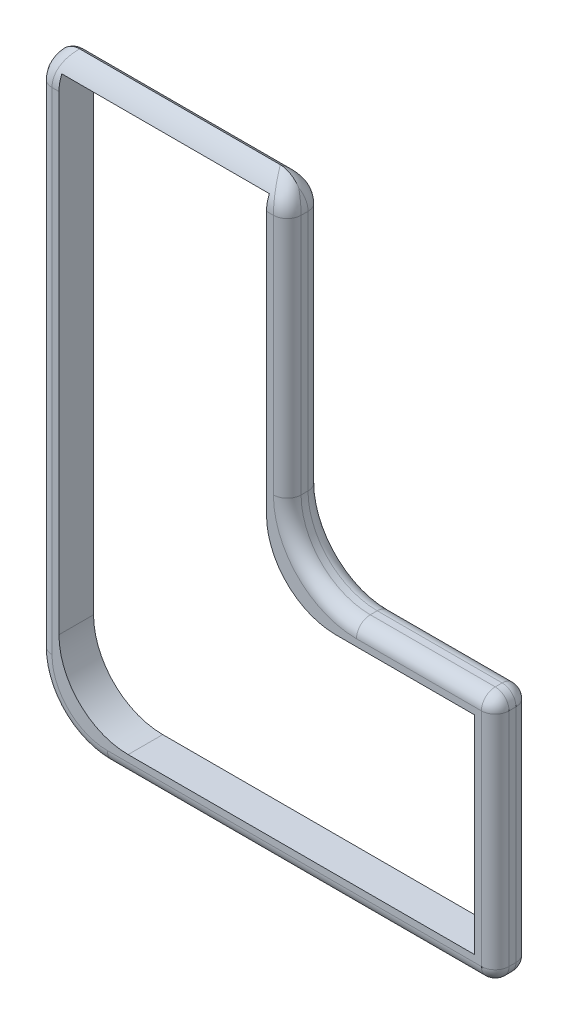
SolidWorks part; units mm, degrees
ref_plane "Front Plane" through (0, 0, 0) normal (0, 0, 1) x (1, 0, 0)
ref_plane "Top Plane" through (0, 0, 0) normal (0, 1, 0) x (1, 0, 0)
ref_plane "Right Plane" through (0, 0, 0) normal (1, 0, 0) x (0, 0, -1)
sketch "Sketch3" plane through (0, 0, 0) normal (0, 0, 1) x (1, 0, 0)
  line L0 (0.15, 0.4) -> (0.15, 0)
  line L1 (-0.15, 0.4) -> (0.15, 0.4)
  line L2 (-0.15, 0.4) -> (-0.15, -0.3)
  line L3 (-0.05, -0.4) -> (0.15, -0.4)
  line L4 (-0.15, 0.43) -> (0.18, 0.43)
  line L5 (-0.15, 0.4) -> (0.15, -0.4) construction
  line L6 (-0.15, -0.4) -> (0.15, 0.4) construction
  line L7 (0.15, -0.4) -> (0.4506, -0.4)
  line L8 (0.15, -0.4) -> (0.15, -0.1)
  line L9 (0.25, -0.1) -> (0.4506, -0.1)
  line L10 (0.4506, -0.4) -> (0.4506, -0.1)
  line L11 (0.18, 0.43) -> (0.18, 0.03)
  line L12 (0.28, -0.07) -> (0.4806, -0.07)
  line L13 (0.4806, -0.07) -> (0.4806, -0.43)
  line L14 (0.4806, -0.43) -> (-0.08, -0.43)
  line L15 (-0.18, -0.33) -> (-0.18, 0.43)
  line L16 (-0.18, 0.43) -> (-0.15, 0.43)
  arc A0 (0.25, -0.1) -> (0.15, 0) centre (0.25, 0) cw
  arc A1 (-0.05, -0.4) -> (-0.15, -0.3) centre (-0.05, -0.3) cw
  arc A2 (0.28, -0.07) -> (0.18, 0.03) centre (0.28, 0.03) cw
  arc A3 (-0.08, -0.43) -> (-0.18, -0.33) centre (-0.08, -0.33) cw
  point P0 (0, 0)
  point P26 (0.28, -0.07)
  point P27 (0.28, -0.07)
  dimension "D4" = 0.1
  dimension "D5" = 0.1
  dimension "D11" = 0.1
  dimension "D12" = 0.1
  dimension "D1" = 0.3
  dimension "D2" = 0.8
  dimension "D3" = 0.3
  dimension "D6" = 0.03
  dimension "D7" = 0.03
  dimension "D8" = 0.03
  dimension "D9" = 0.03
  dimension "D10" = 0.03
  dimension "D13" = 0.03
extrude "Boss-Extrude1" add sketch "Sketch3" along normal mid plane 0.05 contours A3 L14 L13 L12 A2 L11 L4 L16 L15 L3 A1 L2 L1 L0 A0 L9 L10 L7 region at (0.015, 0.4192, 0)
fillet "Fillet1" radius 0.05 4 edges at (0.18, 0.43, 0) (0, 0.43, 0.025) (-0.18, 0.43, 0) (0, 0.43, -0.025)
fillet "Fillet3" radius 0.02 8 edges at (0.1733, 0.405, 0.0183) (0.3803, -0.07, 0.025) (0.2093, -0.0407, 0.025) (0.1733, 0.405, -0.0183) (0.3803, -0.07, -0.025) (0.2093, -0.0407, -0.025) (0.18, 0.205, 0.025) (0.18, 0.205, -0.025)
fillet "Fillet4" radius 0.02 6 edges at (0.4806, -0.0759, -0.0191) (0.4806, -0.26, -0.025) (0.4806, -0.43, 0) (0.4806, -0.26, 0.025) (0.4806, -0.0759, 0.0191) (0.4806, -0.07, 0)
fillet "Fillet5" radius 0.02 10 edges at (0.4747, -0.4241, 0.0191) (-0.1733, 0.405, 0.0183) (-0.18, 0.025, 0.025) (-0.1507, -0.4007, 0.025) (0.4747, -0.4241, -0.0191) (-0.1733, 0.405, -0.0183) (-0.18, 0.025, -0.025) (-0.1507, -0.4007, -0.025) (0.1903, -0.43, 0.025) (0.1903, -0.43, -0.025)
